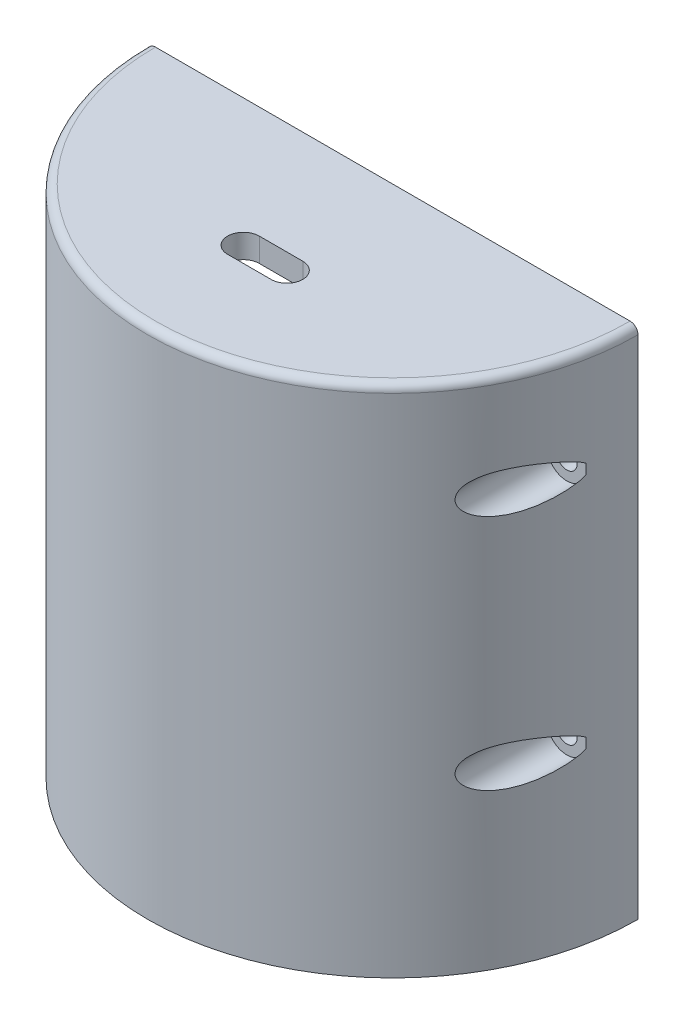
SolidWorks part; units mm, degrees
material "ABS"
ref_plane "Спереди" through (0, 0, 0) normal (0, 0, 1) x (1, 0, 0)
ref_plane "Сверху" through (0, 0, 0) normal (0, 1, 0) x (1, 0, 0)
ref_plane "Справа" through (0, 0, 0) normal (1, 0, 0) x (0, 0, -1)
sketch "Эскиз1" plane through (0, 0, 0) normal (0, 1, 0) x (1, 0, 0)
  line L0 (-31, 0) -> (-28, 0)
  line L1 (28, 0) -> (31, 0)
  arc A2 (31, 0) -> (-31, 0) centre (0, 0) cw
  arc A3 (28, 0) -> (-28, 0) centre (0, 0) cw
  dimension "D1" = 28
  dimension "D2" = 31
extrude "Бобышка-Вытянуть1" add sketch "Эскиз1" along normal blind 65
sketch "Эскиз2" plane through (0, 65, 0) normal (0, 1, 0) x (1, 0, 0)
  line L0 (-31, 0) -> (31, 0)
  arc A3 (31, 0) -> (-31, 0) centre (0, 0) cw
  arc A4 (-31, 0) -> (31, 0) centre (0, 0) ccw construction
sketch "Эскиз12" plane through (0, 0, 0) normal (0, 0, -1) x (-1, 0, 0)
  line L0 (28, 65) -> (28, 0) construction
  line L2 (28, 22) -> (28, 52) construction
  line L4 (28, 22) -> (28, 52) construction
  line L5 (28, 65) -> (28, 0) construction
  line L6 (0, 59.3805) -> (0, 0) construction
  line L7 (-28, 0) -> (28, 0) construction
  line L8 (28, 65) -> (28, 0) construction
  circle A1 centre (28, 52) radius 3
  circle A3 centre (28, 22) radius 3
  circle A4 centre (-28, 52) radius 3
  circle A5 centre (-28, 22) radius 3
  point P8 (28, 37)
  dimension "D3" = 6
  dimension "D1" = 30
  dimension "D2" = 37
extrude "Бобышка-Вытянуть5" add sketch "Эскиз12" against normal up to surface (12.6095 mm away) up to face at (0, 32.5, 14)
sketch "Эскиз16" plane through (0, 0, 0) normal (0, 0, -1) x (-1, 0, 0)
  line L0 (0, 60.4355) -> (0, 0) construction
  circle A1 centre (28, 52) radius 1.3
  circle A3 centre (28, 22) radius 1.3
  circle A4 centre (-28, 22) radius 1.3
  circle A5 centre (-28, 52) radius 1.3
  circle A6 centre (-28, 52) radius 2.5
  circle A7 centre (-28, 22) radius 2.5
  circle A8 centre (28, 22) radius 2.5
  circle A9 centre (28, 52) radius 2.5
  dimension "D1" = 2.6
  dimension "D2" = 5
extrude "Вырез-Вытянуть2" cut sketch "Эскиз16" against normal through all contours A1 | A3 | A4 | A5
extrude "Бобышка-Вытянуть6" add sketch "Эскиз2" against normal blind 3
fillet "Скругление1" radius 1 1 edges at (0, 65, 31)
sketch "Эскиз18" plane through (0, 65, 0) normal (0, 1, 0) x (1, 0, 0)
  line L0 (-2.75, -16.13) -> (2.75, -16.13) construction
  line L1 (-2.75, -14.13) -> (2.75, -14.13)
  line L2 (-2.75, -18.13) -> (2.75, -18.13)
  arc A0 (-2.75, -14.13) -> (-2.75, -18.13) centre (-2.75, -16.13) ccw
  arc A1 (2.75, -18.13) -> (2.75, -14.13) centre (2.75, -16.13) ccw
  point P2 (0, -16.13)
  dimension "D2" = 2
  dimension "D1" = 16.13
  dimension "D3" = 5.5
extrude "Вырез-Вытянуть3" cut sketch "Эскиз18" against normal up to next
extrude "Вырез-Вытянуть4" cut sketch "Эскиз16<4>" against normal through all from offset 6 contours A9 | A7 | A6 | A8 offset against normal yes
sketch "Эскиз16<4>" plane through (0, 0, 0) normal (0, 0, -1) x (-1, 0, 0) same geometry as "Эскиз16"
